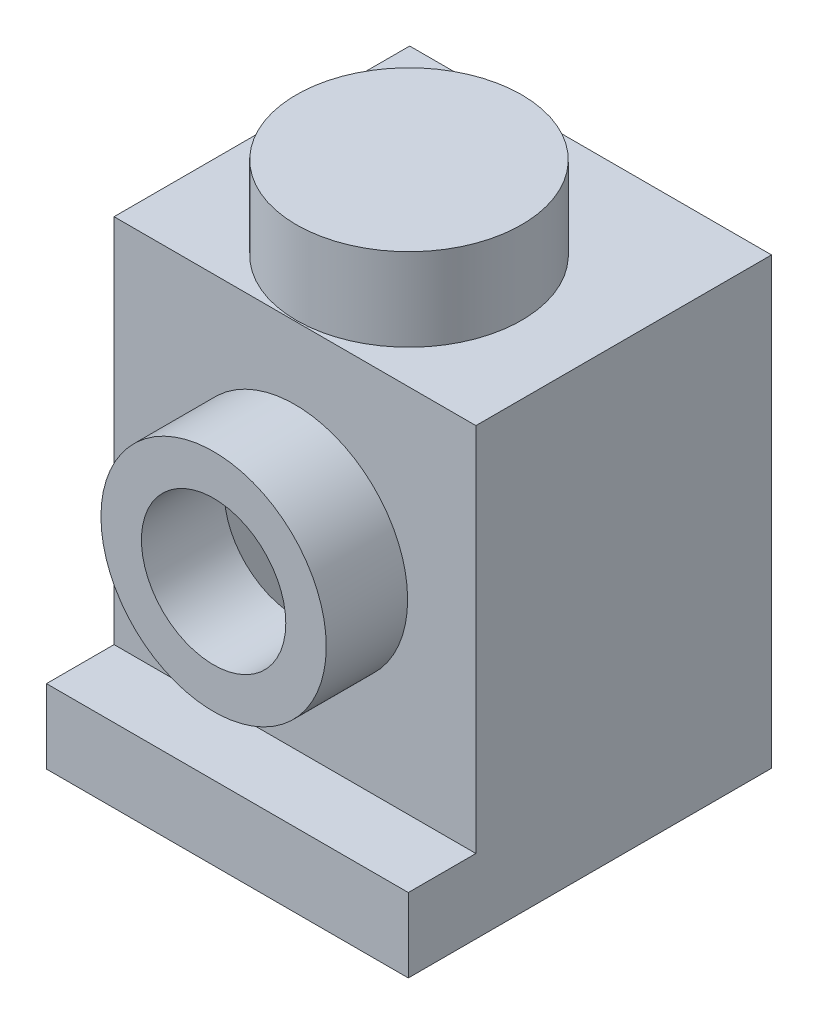
SolidWorks part; units mm, degrees
ref_plane "Front Plane" through (0, 0, 0) normal (0, 0, 1) x (1, 0, 0)
ref_plane "Top Plane" through (0, 0, 0) normal (0, 1, 0) x (1, 0, 0)
ref_plane "Right Plane" through (0, 0, 0) normal (1, 0, 0) x (0, 0, -1)
sketch "Sketch1" plane through (0, 0, 0) normal (1, 0, 0) x (0, 0, -1)
  line L0 (0, 0) -> (0, 9.67)
  line L1 (0, 9.67) -> (-6.43, 9.67)
  line L2 (-6.43, 9.67) -> (-6.43, 1.61)
  line L3 (-6.43, 1.61) -> (-7.9, 1.61)
  line L4 (-7.9, 1.61) -> (-7.9, 0)
  line L5 (-7.9, 0) -> (0, 0)
  point P5 (-7.9, 0.805)
  point P8 (-7.165, 1.61)
  dimension "D1" = 9.67
  dimension "D2" = 7.9
  dimension "D3" = 6.43
  dimension "D4" = 1.61
extrude "Boss-Extrude1" add sketch "Sketch1" against normal blind 7.87
sketch "Sketch2" plane through (0, 9.67, 0) normal (0, 1, 0) x (1, 0, 0)
  line L1 (-7.87, 0) -> (-7.87, -6.43) construction
  line L2 (-7.87, 0) -> (0, 0) construction
  circle A0 centre (-3.935, -3.95) radius 2.45
  dimension "D3" = 4.9
  dimension "D1" = 3.935
  dimension "D2" = 3.95
extrude "Boss-Extrude2" add sketch "Sketch2" along normal blind 1.8
sketch "Sketch3" plane through (0, 0, 6.43) normal (0, 0, 1) x (1, 0, 0)
  line L1 (-7.87, 9.67) -> (-7.87, 1.61) construction
  line L2 (-7.87, 9.67) -> (0, 9.67) construction
  circle A0 centre (-3.935, 5.65) radius 2.45
  circle A1 centre (-3.935, 5.65) radius 1.57
  dimension "D1" = 3.935
  dimension "D2" = 4.02
  dimension "D3" = 4.9
  dimension "D4" = 3.14
extrude "Boss-Extrude3" add sketch "Sketch3" along normal blind 1.77
sketch "Sketch4" plane through (0, 0, 6.43) normal (0, 0, 1) x (1, 0, 0)
  circle A0 centre (-3.935, 5.65) radius 1.57
  dimension "D1" = 3.14
extrude "Cut-Extrude1" cut sketch "Sketch4" against normal through all
sketch "Sketch5" plane through (0, 0, 0) normal (0, 0, -1) x (-1, 0, 0)
  line L0 (1.5, 8.11) -> (6.37, 8.11)
  line L1 (6.37, 8.11) -> (6.37, 3.3)
  line L2 (6.37, 3.3) -> (1.5, 3.3)
  line L3 (1.5, 3.3) -> (1.5, 8.11)
  line L4 (7.87, 9.67) -> (0, 9.67) construction
  line L5 (7.87, 0) -> (0, 0) construction
  line L6 (7.87, 0) -> (7.87, 9.67) construction
  line L7 (0, 0) -> (0, 9.67) construction
  dimension "D1" = 1.56
  dimension "D2" = 3.3
  dimension "D3" = 1.5
  dimension "D4" = 1.5
extrude "Cut-Extrude2" cut sketch "Sketch5" against normal blind 4.92
sketch "Sketch6" plane through (0, 0, 0) normal (0, -1, 0) x (1, 0, 0)
  line L0 (-6.42, 6.4) -> (-1.45, 6.4)
  line L1 (-1.45, 6.4) -> (-1.45, 1.5)
  line L2 (-1.45, 1.5) -> (-6.42, 1.5)
  line L3 (-6.42, 1.5) -> (-6.42, 6.4)
  line L4 (-7.87, 7.9) -> (-7.87, 0) construction
  line L5 (0, 7.9) -> (0, 0) construction
  line L6 (-7.87, 0) -> (0, 0) construction
  line L7 (-7.87, 7.9) -> (0, 7.9) construction
  dimension "D1" = 1.45
  dimension "D2" = 1.45
  dimension "D3" = 1.5
  dimension "D4" = 1.5
extrude "Cut-Extrude3" cut sketch "Sketch6" against normal blind 8.81
shell "Shell1" thickness 1.5 removed face at (-3.935, 8.81, 3.95)
